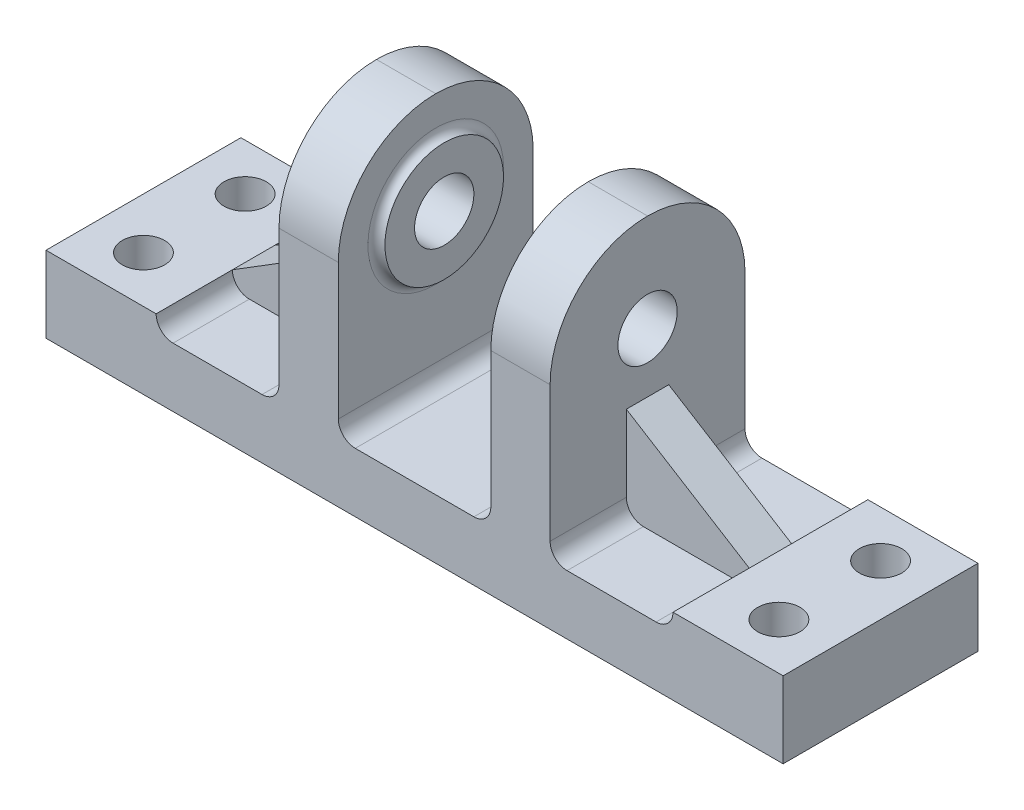
SolidWorks part; units mm, degrees
ref_plane "Front Plane" through (0, 0, 0) normal (0, 0, 1) x (1, 0, 0)
ref_plane "Top Plane" through (0, 0, 0) normal (0, 1, 0) x (1, 0, 0)
ref_plane "Right Plane" through (0, 0, 0) normal (1, 0, 0) x (0, 0, -1)
sketch "Sketch1" plane through (0, 0, 0) normal (0, 0, 1) x (1, 0, 0)
  line L0 (-87, 0) -> (-87, 18)
  line L1 (-87, 18) -> (-61, 18)
  line L2 (-61, 18) -> (-61, 14)
  line L3 (-61, 14) -> (-32, 14)
  line L4 (-32, 14) -> (-32, 73)
  line L5 (-32, 73) -> (-18, 73)
  line L6 (-18, 73) -> (-18, 14)
  line L7 (-18, 14) -> (18, 14)
  line L8 (0, -55) -> (0, 55) construction
  line L9 (18, 73) -> (18, 14)
  line L10 (32, 73) -> (18, 73)
  line L11 (32, 14) -> (32, 73)
  line L12 (61, 14) -> (32, 14)
  line L13 (61, 18) -> (61, 14)
  line L14 (87, 18) -> (61, 18)
  line L15 (87, 0) -> (87, 18)
  line L16 (-87, 0) -> (87, 0)
  point P12 (0, 14)
  dimension "D1" = 18
  dimension "D2" = 14
  dimension "D3" = 14
  dimension "D4" = 36
  dimension "D5" = 174
  dimension "D6" = 26
  dimension "D7" = 73
extrude "Boss-Extrude1" add sketch "Sketch1" along normal mid plane 46
fillet "Fillet1" radius 23 4 edges at (-25, 73, 23) (-25, 73, -23) (25, 73, -23) (25, 73, 23)
sketch "Sketch2" plane through (-18, 0, 0) normal (1, 0, 0) x (0, 0, -1)
  circle A0 centre (0, 50) radius 14
  dimension "D1" = 28
extrude "Boss-Extrude2" add sketch "Sketch2" along normal blind 2
mirror "Mirror1" about plane through (0, 0, 0) normal (1, 0, 0) of "Boss-Extrude2"
hole_wizard "Hole1" positions "Sketch3" profile "Sketch4" legacy end condition through all
sketch "Sketch3" plane through (32, 0, 0) normal (1, 0, 0) x (0, 0, -1)
  point P0 (0, 50)
sketch "Sketch4" plane through (32, 50, 0) normal (0, 1, 0) x (0, 0, -1)
  line L0 (0, 0) -> (0, 119)
  line L1 (0, 119) -> (7, 119)
  line L2 (7, 119) -> (7, 0)
  line L3 (7, 0) -> (0, 0)
  line L4 (0, 110) -> (0, -10) construction
  dimension "Diameter" = 14
  dimension "Depth" = 119
fillet "Fillet2" radius 2 2 edges at (18, 64, 0) (-18, 36, 0)
fillet "Fillet3" radius 4 6 edges at (-32, 14, 0) (18, 14, 0) (61, 14, 0) (32, 14, 0) (-18, 14, 0) (-61, 14, 0)
sketch "Sketch5" plane through (0, 0, 0) normal (0, 0, 1) x (1, 0, 0)
  line L0 (61, 18) -> (32, 36)
  line L1 (32, 18) -> (32, 50) construction
  line L3 (57, 14) -> (36, 14) construction
  dimension "D1" = 22
rib "Rib1" sketch "Sketch5" sketch "Sketch5" thickness 10 extrusion direction parallel to sketch draft on no parameters "D1"=10
mirror "Mirror2" about plane through (0, 0, 0) normal (1, 0, 0) of "Rib1"
hole_wizard "Hole2" positions "Sketch6" profile "Sketch7" legacy end condition through all
sketch "Sketch6" plane through (0, 18, 0) normal (0, 1, 0) x (1, 0, 0)
  point P0 (75, 12)
  point P2 (75, -12)
  point P6 (0, 0)
  dimension "D1" = 24
  dimension "D2" = 12
  dimension "D3" = 75
sketch "Sketch7" plane through (75, 18, -12) normal (1, 0, 0) x (0, 0, 1)
  line L0 (0, 0) -> (0, 18)
  line L1 (0, 18) -> (5, 18)
  line L2 (5, 18) -> (5, 0)
  line L3 (5, 0) -> (0, 0)
  line L4 (0, 110) -> (0, -10) construction
  dimension "Diameter" = 10
  dimension "Depth" = 18
mirror "Mirror3" about plane through (0, 0, 0) normal (1, 0, 0) of "Hole2"
